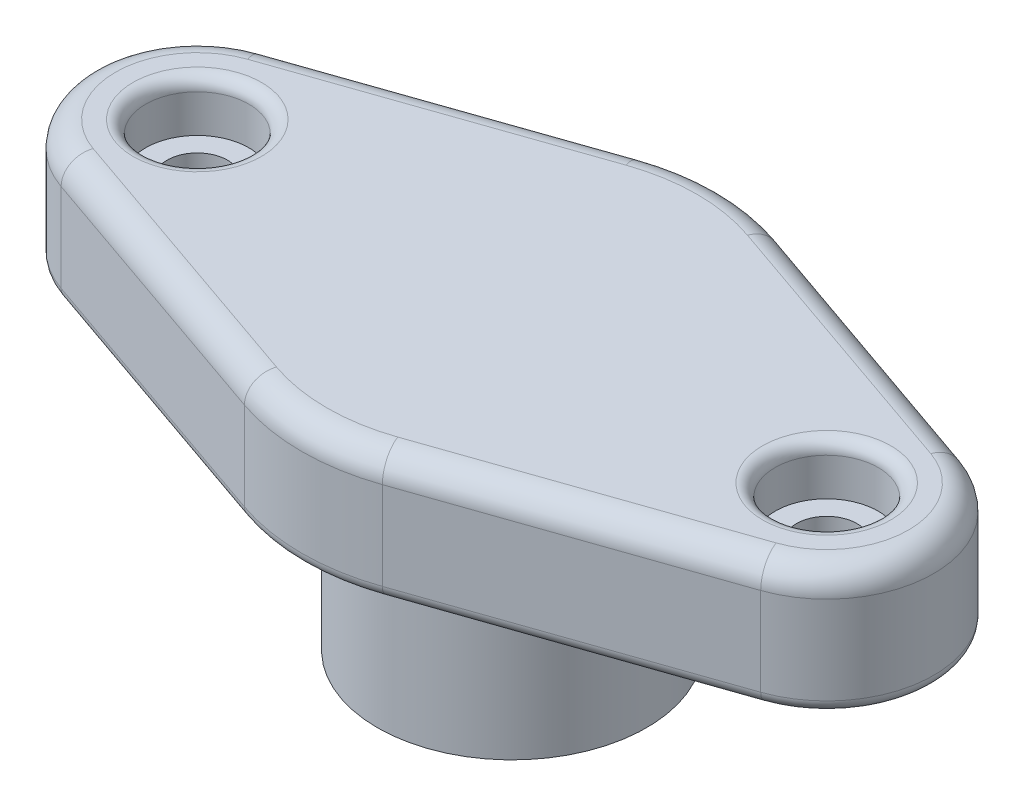
SolidWorks part; units mm, degrees
ref_plane "Front Plane" through (0, 0, 0) normal (0, 0, 1) x (1, 0, 0)
ref_plane "Top Plane" through (0, 0, 0) normal (0, 1, 0) x (1, 0, 0)
ref_plane "Right Plane" through (0, 0, 0) normal (1, 0, 0) x (0, 0, -1)
sketch "Sketch1" plane through (0, 0, 0) normal (0, 1, 0) x (1, 0, 0)
  circle A0 centre (0, 0) radius 5.35
  dimension "D1" = 10.7
extrude "Boss-Extrude1" add sketch "Sketch1" along normal blind 7
sketch "Sketch2" plane through (0, 7, 0) normal (0, 1, 0) x (1, 0, 0)
  line L0 (-12.5, 0) -> (12.5, 0) construction
  line L1 (2.7388, 7.8881) -> (13.894, 4.0149)
  line L2 (-2.7388, -7.8881) -> (-13.894, -4.0149)
  line L3 (13.894, -4.0149) -> (2.7388, -7.8881)
  line L7 (-13.894, 4.0149) -> (-2.7388, 7.8881)
  arc A0 (-2.7388, -7.8881) -> (2.7388, -7.8881) centre (0, 0) ccw
  circle A2 centre (12.5, 0) radius 1.2
  circle A3 centre (-12.5, 0) radius 1.2
  arc A4 (13.894, -4.0149) -> (13.894, 4.0149) centre (12.5, 0) ccw
  arc A7 (2.7388, 7.8881) -> (-2.7388, 7.8881) centre (0, 0) ccw
  arc A9 (-13.894, 4.0149) -> (-13.894, -4.0149) centre (-12.5, 0) ccw
  point P5 (0, 0)
  dimension "D1" = 16.7
  dimension "D2" = 2.4
  dimension "D3" = 2.4
  dimension "D5" = 8.35
  dimension "D6" = 8.5
  dimension "D7" = 4.25
  dimension "D4" = 25
extrude "Boss-Extrude2" add sketch "Sketch2" along normal blind 5
sketch "Sketch3" plane through (0, 12, 0) normal (0, 1, 0) x (1, 0, 0)
  circle A0 centre (-12.5, 0) radius 2.05
  circle A1 centre (12.5, 0) radius 2.05
  dimension "D1" = 4.1
  dimension "D2" = 4.1
extrude "Cut-Extrude1" cut sketch "Sketch3" against normal blind 2
fillet "Fillet1" radius 0.5 10 edges at (12.5, 12, 2.05) (-12.5, 12, 2.05) (-16.75, 7, 0) (-8.3164, 7, -5.9515) (0, 7, -8.35) (8.3164, 7, -5.9515) (16.75, 7, 0) (8.3164, 7, 5.9515) (0, 7, 8.35) (-8.3164, 7, 5.9515)
fillet "Fillet2" radius 1 8 edges at (-8.3164, 12, -5.9515) (0, 12, -8.35) (8.3164, 12, -5.9515) (16.75, 12, 0) (8.3164, 12, 5.9515) (0, 12, 8.35) (-8.3164, 12, 5.9515) (-16.75, 12, 0)
sketch "Sketch4" plane through (0, 0, 0) normal (0, -1, 0) x (1, 0, 0)
  circle A0 centre (0, 0) radius 3.5
  dimension "D1" = 7
extrude "Cut-Extrude2" cut sketch "Sketch4" against normal blind 2
fillet "Fillet3" radius 1 2 edges at (0, 0, -3.5) (0, 2, -3.5)
